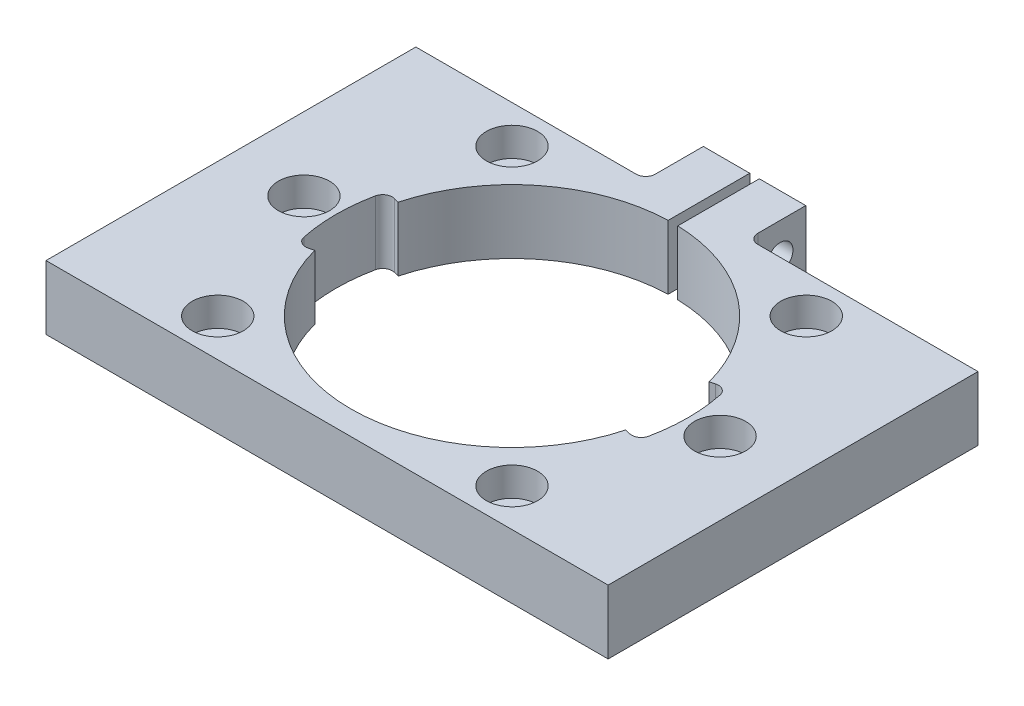
SolidWorks part; units mm, degrees
material "6061 Alloy"
ref_plane "Front Plane" through (0, 0, 0) normal (0, 0, 1) x (1, 0, 0)
ref_plane "Top Plane" through (0, 0, 0) normal (0, 1, 0) x (1, 0, 0)
ref_plane "Right Plane" through (0, 0, 0) normal (1, 0, 0) x (0, 0, -1)
sketch "Sketch1" plane through (0, 76, 0) normal (0, 1, 0) x (1, 0, 0)
  line L0 (-25.0722, 6.7181) -> (25.0722, -6.7181)
  line L1 (-43.9014, -28.8858) -> (43.9014, -28.8858)
  line L2 (-43.9014, -28.8858) -> (-43.9014, 28.8858)
  line L3 (-43.9014, 28.8858) -> (43.9014, 28.8858)
  line L4 (43.9014, -28.8858) -> (43.9014, 28.8858)
  line L5 (-43.9014, -28.8858) -> (43.9014, 28.8858) construction
  line L6 (-43.9014, 28.8858) -> (43.9014, -28.8858) construction
  line L7 (-25.0722, -6.7181) -> (25.0722, 6.7181)
  line L8 (-77, 0) -> (77, 0) construction
  circle A0 centre (0, 0) radius 25.15
  arc A1 (-26.9293, 5.5732) -> (-26.9293, -5.5732) centre (0, 0) ccw
  arc A2 (26.9293, 5.5732) -> (26.9293, -5.5732) centre (0, 0) cw
  circle A3 centre (0, 0) radius 27.5 construction
  arc A4 (25.0722, -6.7181) -> (26.9293, -5.5732) centre (25.4605, -5.2692) ccw
  arc A5 (25.0722, 6.7181) -> (26.9293, 5.5732) centre (25.4605, 5.2692) cw
  arc A6 (-25.0722, -6.7181) -> (-26.9293, -5.5732) centre (-25.4605, -5.2692) cw
  arc A7 (-25.0722, 6.7181) -> (-26.9293, 5.5732) centre (-25.4605, 5.2692) ccw
  circle A8 centre (22.981, 22.981) radius 2 construction
  circle A9 centre (32.5, 0) radius 2 construction
  circle A10 centre (22.981, -22.981) radius 2 construction
  circle A11 centre (-22.981, -22.981) radius 2 construction
  circle A12 centre (-32.5, 0) radius 2 construction
  circle A13 centre (-22.981, 22.981) radius 2 construction
  circle A14 centre (22.981, 22.981) radius 2
  circle A15 centre (32.5, 0) radius 2
  circle A16 centre (22.981, -22.981) radius 2
  circle A17 centre (-22.981, -22.981) radius 2
  circle A18 centre (-32.5, 0) radius 2
  circle A19 centre (-22.981, 22.981) radius 2
  point P0 (0, 0)
  dimension "D1" = 50.3
  dimension "D4" = 1.5
  dimension "D2" = 15
  dimension "D3" = 15
extrude "Boss-Extrude1" add sketch "Sketch1" along normal blind 10 contours L1 L4 L3 L2 A19 A18 A17 A16 A15 A14 A7 L0 A0 L7 A5 A2 A4 A6 A1 region at (-42.8504, 76, 0)
sketch "Sketch2" plane through (0, 86, 0) normal (0, 1, 0) x (1, 0, 0)
  line L0 (0, -116.875) -> (0, 116.875) construction
  line L1 (-8, 37.8858) -> (8, 37.8858)
  line L2 (-8, 37.8858) -> (-8, 28.8858)
  line L3 (-8, 28.8858) -> (8, 28.8858)
  line L4 (8, 37.8858) -> (8, 28.8858)
  line L5 (-8, 37.8858) -> (8, 28.8858) construction
  line L6 (-8, 28.8858) -> (8, 37.8858) construction
  line L7 (-43.9014, 28.8858) -> (43.9014, 28.8858) construction
  point P0 (0, 33.3858)
  dimension "D1" = 9
  dimension "D2" = 16
extrude "Boss-Extrude2" add sketch "Sketch2" against normal blind 10
sketch "Sketch3" plane through (0, 86, 0) normal (0, 1, 0) x (1, 0, 0)
  line L0 (0, -116.875) -> (0, 116.875) construction
  line L1 (-0.75, 23.8858) -> (0.75, 23.8858)
  line L2 (-0.75, 23.8858) -> (-0.75, 37.8858)
  line L3 (-0.75, 37.8858) -> (0.75, 37.8858)
  line L4 (0.75, 23.8858) -> (0.75, 37.8858)
  line L5 (-0.75, 23.8858) -> (0.75, 37.8858) construction
  line L6 (-0.75, 37.8858) -> (0.75, 23.8858) construction
  line L7 (8, 37.8858) -> (-8, 37.8858) construction
  point P0 (0, 30.8858)
  dimension "D1" = 14
  dimension "D2" = 1.5
extrude "Cut-Extrude1" cut sketch "Sketch3" against normal blind 10
sketch "Sketch4" plane through (8, 0, 0) normal (1, 0, 0) x (0, 0, -1)
  line L0 (33.8858, 81) -> (37.8858, 81) construction
  line L1 (37.8858, 76) -> (37.8858, 86) construction
  circle A0 centre (33.8858, 81) radius 2
  dimension "D1" = 4
  dimension "D2" = 4
extrude "Cut-Extrude2" cut sketch "Sketch4" against normal up to vertex (7.25 mm away) up to point (0.75, 86, -37.8858)
sketch "Sketch5" plane through (-0.75, 0, 0) normal (1, 0, 0) x (0, 0, -1)
  circle A0 centre (33.8858, 81) radius 1.6
  dimension "D1" = 3.2
extrude "Cut-Extrude3" cut sketch "Sketch5" against normal blind 10
sketch "Sketch7" plane through (0, 86, 0) normal (0, 1, 0) x (1, 0, 0)
  circle A0 centre (-22.981, 22.981) radius 4
  circle A1 centre (22.981, 22.981) radius 4
  circle A2 centre (32.5, 0) radius 4
  circle A3 centre (-32.5, 0) radius 4
  circle A4 centre (-22.981, -22.981) radius 4
  circle A5 centre (22.981, -22.981) radius 4
  dimension "D1" = 8
extrude "Cut-Extrude4" cut sketch "Sketch7" against normal blind 4.5
fillet "Fillet1" radius 1.5 2 edges at (-8, 81, -28.8858) (8, 81, -28.8858)
